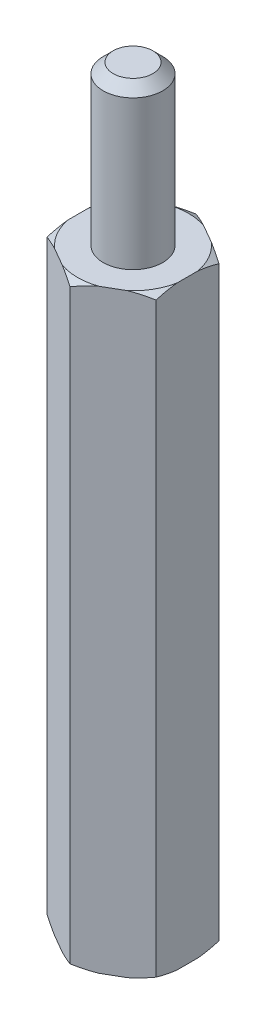
SolidWorks part; units mm, degrees
material "Латунь"
ref_plane "Спереди" through (0, 0, 0) normal (0, 0, 1) x (1, 0, 0)
ref_plane "Сверху" through (0, 0, 0) normal (0, 1, 0) x (1, 0, 0)
ref_plane "Справа" through (0, 0, 0) normal (1, 0, 0) x (0, 0, -1)
sketch "Эскиз1" plane through (0, 0, 0) normal (0, 1, 0) x (1, 0, 0)
  line L1 (0, 3.1754) -> (-2.75, 1.5877)
  line L2 (-2.75, 1.5877) -> (-2.75, -1.5877)
  line L3 (-2.75, -1.5877) -> (0, -3.1754)
  line L4 (0, -3.1754) -> (2.75, -1.5877)
  line L5 (2.75, -1.5877) -> (2.75, 1.5877)
  line L6 (2.75, 1.5877) -> (0, 3.1754)
  circle A0 centre (0, 0) radius 1.5
  circle A1 centre (0, 0) radius 2.75 construction
  dimension "D1" = 5.5
  dimension "D2" = 3
extrude "Бобышка-Вытянуть1" add sketch "Эскиз1" along normal blind 30 contours A0 | L5 L6 L1 L2 L3 L4 A0 region at (1.333, 0, -2.3088) region at (0, 0, 0)
sketch "Эскиз2" plane through (0, 0, 0) normal (1, 0, 0) x (0, 0, -1)
  line L0 (0, 0) -> (-2.8, 0)
  line L2 (-2.8, 0) -> (-26.1607, 13.4873)
  line L3 (-26.1607, 13.4873) -> (-26.1607, 0)
  line L4 (-26.1607, 0) -> (-2.8, 0)
  line L5 (0, 30) -> (-2.8, 30)
  line L7 (-2.8, 30) -> (-26.1607, 30)
  line L8 (-26.1607, 30) -> (-26.1607, 16.5127)
  line L9 (-26.1607, 16.5127) -> (-2.8, 30)
  line L10 (0, 30) -> (0, 9.6596) construction
  dimension "D1" = 2.8
  dimension "D2" = 2.8
  dimension "D3" = 30
  dimension "D4" = 30
revolve "Вырез-Повернуть1" cut sketch "Эскиз2" angle 360 about L10 region at (0, 4.4958, 18.3738) region at (0, 25.5042, 18.3738)
sketch "Эскиз3" plane through (0, 30, 0) normal (0, 1, 0) x (1, 0, 0)
  circle A0 centre (0, 0) radius 1.5
extrude "Бобышка-Вытянуть2" add sketch "Эскиз3" along normal blind 8
chamfer "Фаска1" distance 0.5 angle 45 1 edges at (0, 38, 1.5)
extrude "Вырез-Вытянуть1" cut sketch "Эскиз1<3>" along normal blind 8 contours A0 region at (0, 0, 0)
sketch "Эскиз1<3>" plane through (0, 0, 0) normal (0, 1, 0) x (1, 0, 0) same geometry as "Эскиз1"
